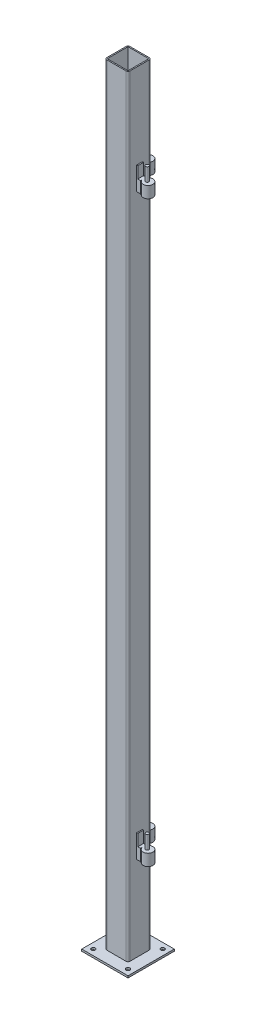
SolidWorks part; units mm, degrees
ref_plane "前视" through (0, 0, 0) normal (0, 0, 1) x (1, 0, 0)
ref_plane "上视" through (0, 0, 0) normal (0, 1, 0) x (1, 0, 0)
ref_plane "右视" through (0, 0, 0) normal (1, 0, 0) x (0, 0, -1)
sketch "草图1" plane through (0, 0, 0) normal (0, 1, 0) x (1, 0, 0)
  line L0 (0, 0) -> (0, 57.1093) construction
  line L1 (-60, 60) -> (60, 60)
  line L2 (-60, 60) -> (-60, -60)
  line L3 (-60, -60) -> (60, -60)
  line L4 (60, 60) -> (60, -60)
  line L5 (0, 0) -> (82.0444, 0) construction
  dimension "D1" = 120
  dimension "D2" = 120
extrude "凸台-拉伸1" add sketch "草图1" along normal blind 5
sketch "草图2" plane through (0, 5, 0) normal (0, 1, 0) x (1, 0, 0)
  line L13 (-30, 60) -> (-30, -60)
  line L14 (-30, 30) -> (-30, -30)
  line L20 (27, 27) -> (-27, 27)
  line L21 (-27, 27) -> (-27, -27)
  line L22 (-27, -27) -> (27, -27)
  line L23 (-60, -30) -> (30, -30)
  line L24 (30, -30) -> (30, 30)
  line L25 (30, 30) -> (-60, 30)
  line L26 (-30, -30) -> (30, -30)
  line L27 (30, -30) -> (30, 30)
  line L28 (30, 30) -> (-30, 30)
  line L29 (27, -27) -> (27, 27)
  dimension "D1" = 30
  dimension "D2" = 30
  dimension "D3" = 3
extrude "凸台-拉伸2" add sketch "草图2" along normal blind 2000
fillet "圆角1" radius 5 4 edges at (-30, 1005, 30) (30, 1005, 30) (-30, 1005, -30) (30, 1005, -30)
sketch "草图3" plane through (0, 5, 0) normal (0, 1, 0) x (1, 0, 0)
  circle A0 centre (-45, 45) radius 5
  circle A1 centre (45, 45) radius 5
  circle A2 centre (-45, -45) radius 5
  circle A3 centre (45, -45) radius 5
  dimension "D1" = 10
  dimension "D2" = 90
  dimension "D3" = 45
  dimension "D4" = 90
  dimension "D5" = 45
extrude "切除-拉伸1" cut sketch "草图3" against normal blind 2000
ref_plane "基准面1" through (0, 0, 0) normal (1, 0, 0) x (0, 0, -1)
sketch "草图6" plane through (0, 0, 0) normal (1, 0, 0) x (0, 0, -1)
  line L0 (30, 2005) -> (30, 5) construction
  line L1 (30, 1785) -> (30, 1725)
  line L2 (30, 1785) -> (33, 1785)
  line L3 (33, 1785) -> (33, 1755)
  line L4 (33, 1755) -> (40, 1755)
  line L5 (40, 1755) -> (40, 1725)
  line L6 (40, 1725) -> (30, 1725)
  line L7 (-25, 2005) -> (25, 2005) construction
  dimension "D1" = 30
  dimension "D2" = 60
  dimension "D3" = 10
  dimension "D4" = 3
  dimension "D5" = 220
extrude "凸台-拉伸5" add sketch "草图6" along normal mid plane 15
pattern_linear "阵列(线性)1" count 2 spacing 1500 along (0, -1, 0) of "凸台-拉伸5"
sketch "草图7" plane through (0, 1755, 0) normal (0, 1, 0) x (1, 0, 0)
  line L0 (7.5, 40) -> (-7.5, 40) construction
  circle A0 centre (0, 52) radius 12.5
  dimension "D1" = 25
  dimension "D2" = 12
extrude "凸台-拉伸6" add sketch "草图7" against normal blind 30
sketch "草图8" plane through (0, 1755, 0) normal (0, 1, 0) x (1, 0, 0)
  circle A0 centre (0, 50) radius 4
  arc A1 (3.5, 40) -> (-3.5, 40) centre (0, 52) ccw construction
  dimension "D2" = 8
  dimension "D1" = 2
extrude "凸台-拉伸7" add sketch "草图8" along normal blind 35
pattern_linear "阵列(线性)2" count 2 spacing 1500 along (0, -1, 0) of "凸台-拉伸7", "凸台-拉伸6"
ref_plane "基准面2" through (0, 0, 0) normal (-1, 0, 0) x (0, 0, 1)
ref_plane "基准面3" through (0, 0, 0) normal (0, 0, 1) x (1, 0, 0)
ref_axis "基准轴1" through (0, 2105, 0) along (0, -1, 0)
pattern_circular "阵列(圆周)2" count 2 every 90 about axis through (0, 2105, 0) along (0, -1, 0) of "凸台-拉伸5", "凸台-拉伸6", "凸台-拉伸7", "阵列(线性)1", "阵列(线性)2"
